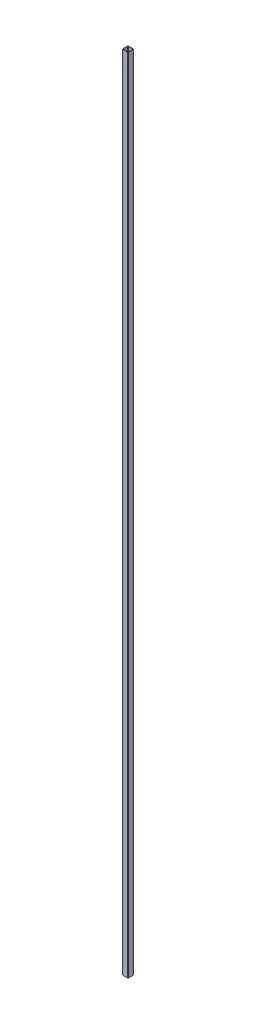
SolidWorks part; units mm, degrees
material "Hexcel AS4C (3000 Filaments)"
ref_plane "Front Plane" through (0, 0, 0) normal (0, 0, 1) x (1, 0, 0)
ref_plane "Top Plane" through (0, 0, 0) normal (0, 1, 0) x (1, 0, 0)
ref_plane "Right Plane" through (0, 0, 0) normal (1, 0, 0) x (0, 0, -1)
sketch "Sketch1" plane through (0, 0, 0) normal (0, 1, 0) x (1, 0, 0)
  line L1 (-3, -4) -> (3, -4)
  line L2 (-4, -3) -> (-4, 3)
  line L3 (-3, 4) -> (3, 4)
  line L4 (4, -3) -> (4, 3)
  line L5 (-4, -4) -> (4, 4) construction
  line L6 (-4, 4) -> (4, -4) construction
  line L7 (-2.5, -3.5) -> (2.5, -3.5)
  line L8 (-3.5, -2.5) -> (-3.5, 2.5)
  line L9 (-2.5, 3.5) -> (2.5, 3.5)
  line L10 (3.5, -2.5) -> (3.5, 2.5)
  line L11 (-3.5, -3.5) -> (3.5, 3.5) construction
  line L12 (-3.5, 3.5) -> (3.5, -3.5) construction
  arc A0 (-3, -4) -> (-4, -3) centre (-3, -3) cw
  arc A1 (3, 4) -> (4, 3) centre (3, 3) cw
  arc A2 (3, -4) -> (4, -3) centre (3, -3) ccw
  arc A3 (-4, 3) -> (-3, 4) centre (-3, 3) cw
  arc A4 (-2.5, -3.5) -> (-3.5, -2.5) centre (-2.5, -2.5) cw
  arc A5 (2.5, -3.5) -> (3.5, -2.5) centre (2.5, -2.5) ccw
  arc A6 (2.5, 3.5) -> (3.5, 2.5) centre (2.5, 2.5) cw
  arc A7 (-3.5, 2.5) -> (-2.5, 3.5) centre (-2.5, 2.5) cw
  point P0 (0, 0)
  point P18 (0, 0)
  dimension "D3" = 1
  dimension "D6" = 1
  dimension "D7" = 1
  dimension "D8" = 1
  dimension "D9" = 1
  dimension "D1" = 8
  dimension "D2" = 8
  dimension "D4" = 0.5
  dimension "D5" = 0.5
extrude "Boss-Extrude1" add sketch "Sketch1" along normal blind 1100
